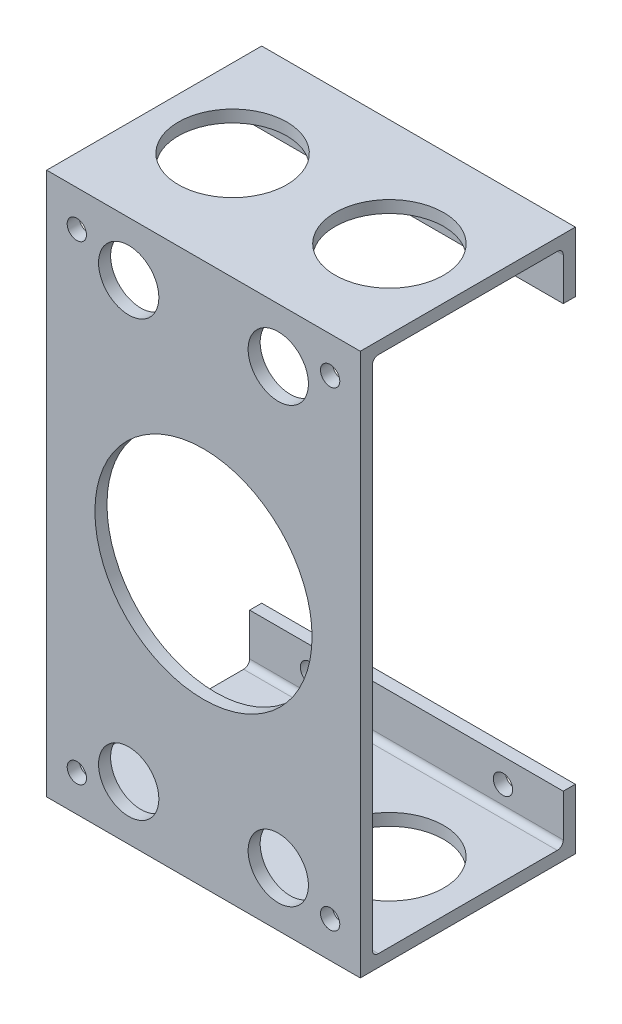
SolidWorks part; units mm, degrees
ref_plane "Top Plane" through (0, 0, 0) normal (0, 0, 1) x (1, 0, 0)
ref_plane "Right Plane" through (0, 0, 0) normal (0, 1, 0) x (1, 0, 0)
ref_plane "Front Plane" through (0, 0, 0) normal (1, 0, 0) x (0, 0, -1)
sketch "Sketch1" plane through (0, 0, 0) normal (1, 0, 0) x (0, 0, -1)
  line L0 (0, -45) -> (0, 45)
  line L1 (0, -45) -> (35.6544, -45)
  line L2 (35.6544, -45) -> (35.6544, -35)
  line L3 (-52.6834, 0) -> (59.8675, 0) construction
  line L4 (35.6544, 45) -> (35.6544, 35)
  line L5 (0, 45) -> (35.6544, 45)
  line L6 (33.6544, 43) -> (33.6544, 35)
  line L7 (2, 43) -> (33.6544, 43)
  line L8 (2, -43) -> (2, 43)
  line L9 (2, -43) -> (33.6544, -43)
  line L10 (33.6544, -43) -> (33.6544, -35)
  line L11 (33.6544, -35) -> (35.6544, -35)
  line L12 (33.6544, 35) -> (35.6544, 35)
  point P12 (0, 0)
  dimension "D1" = 35.6544
  dimension "D2" = 10
  dimension "D3" = 90
  dimension "D4" = 2
extrude "Boss-Extrude1" add sketch "Sketch1" along normal mid plane 52
sketch "Sketch2" plane through (0, 0, 0) normal (0, 0, 1) x (1, 0, 0)
  line L0 (-30.8424, 0) -> (30.398, 0) construction
  line L1 (0, -48.7968) -> (0, 47.6414) construction
  circle A0 centre (-21, -39) radius 1.6
  circle A1 centre (-21, 39) radius 1.6
  circle A2 centre (21, 39) radius 1.6
  circle A3 centre (21, -39) radius 1.6
  dimension "D1" = 78
  dimension "D3" = 3.2
  dimension "D2" = 42
extrude "Cut-Extrude1" cut sketch "Sketch2" against normal up to next
sketch "Sketch3" plane through (0, 0, 0) normal (0, 0, 1) x (1, 0, 0)
  line L0 (26, 45) -> (26, -45) construction
  circle A0 centre (0, 0) radius 18
  dimension "D1" = 8
extrude "Cut-Extrude2" cut sketch "Sketch3" against normal up to next
sketch "Sketch4" plane through (0, -45, 0) normal (0, -1, 0) x (1, 0, 0)
  line L0 (0, 0) -> (0, -35.6544) construction
  line L3 (26, 0) -> (26, -35.6544) construction
  line L4 (26, -35.6544) -> (-26, -35.6544) construction
  circle A0 centre (-13, -17.8272) radius 9
  circle A1 centre (13, -17.8272) radius 9
  point P9 (0, -17.8272)
  point P10 (0, 0)
  point P11 (0, 0)
  point P12 (0, -35.6544)
  dimension "D1" = 8
  dimension "D2" = 4
extrude "Cut-Extrude3" cut sketch "Sketch4" against normal through all
sketch "Sketch5" plane through (0, 0, 0) normal (0, 0, 1) x (1, 0, 0)
  line L0 (-30.6647, 0) -> (33.5216, 0) construction
  line L1 (0, -51.5205) -> (0, 55.9011) construction
  line L6 (26, -45) -> (-26, -45) construction
  circle A0 centre (-12.4, -36) radius 5
  circle A1 centre (-12.4, 36) radius 5
  circle A2 centre (12.4, 36) radius 5
  circle A3 centre (12.4, -36) radius 5
  circle A6 centre (-21, -39) radius 1.6 construction
  dimension "D1" = 4
  dimension "D2" = 2
  dimension "D3" = 10
extrude "Cut-Extrude4" cut sketch "Sketch5" against normal up to next
sketch "Sketch6" plane through (0, 0, -33.6544) normal (0, 0, 1) x (1, 0, 0)
  line L0 (0, 47.5711) -> (0, -51.6381) construction
  line L1 (-35.4935, 0) -> (38.6978, 0) construction
  circle A0 centre (16, -39) radius 1.6
  circle A1 centre (-16, -39) radius 1.6
  circle A2 centre (-16, 39) radius 1.6
  circle A3 centre (16, 39) radius 1.6
  dimension "D1" = 3.2
  dimension "D2" = 32
  dimension "D3" = 78
extrude "Cut-Extrude5" cut sketch "Sketch6" against normal up to next
fillet "Fillet1" radius 1 4 edges at (0, -43, -2) (0, 43, -2) (0, -43, -33.6544) (0, 43, -33.6544)
